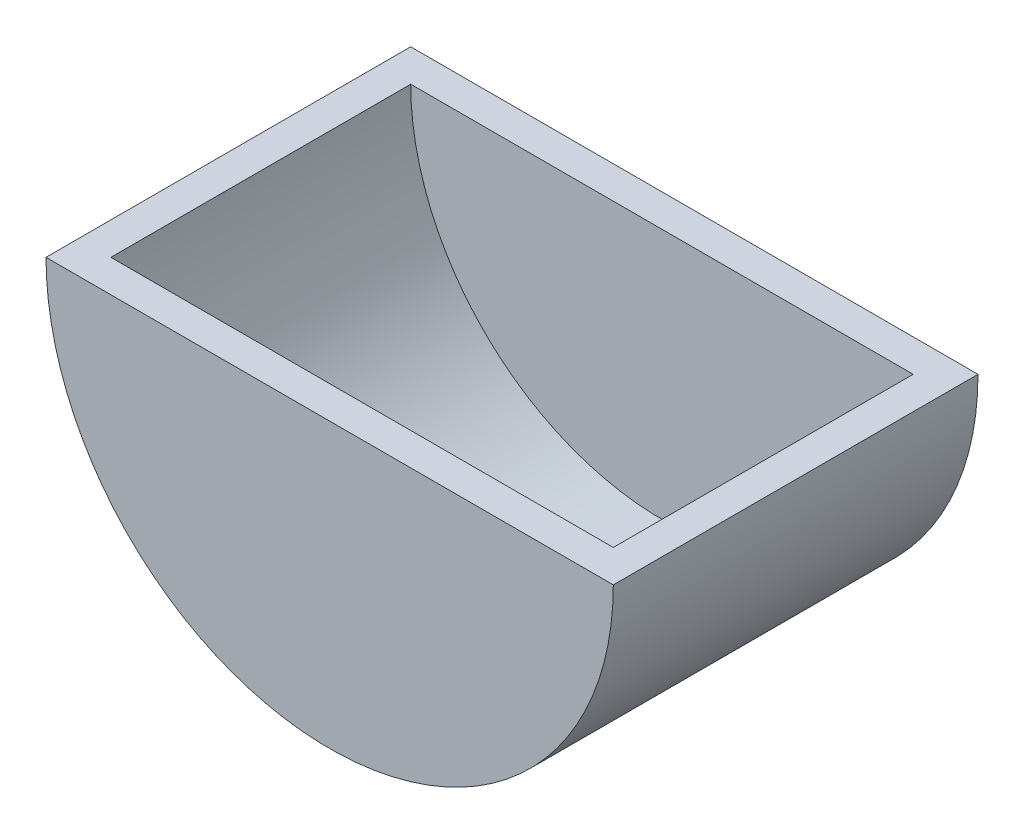
SolidWorks part; units mm, degrees
ref_plane "Front Plane" through (0, 0, 0) normal (0, 0, 1) x (1, 0, 0)
ref_plane "Top Plane" through (0, 0, 0) normal (0, 1, 0) x (1, 0, 0)
ref_plane "Right Plane" through (0, 0, 0) normal (1, 0, 0) x (0, 0, -1)
sketch "Sketch1" plane through (0, 0, 0) normal (0, 0, 1) x (1, 0, 0)
  line L0 (-35, 0) -> (35, 0)
  circle A0 centre (0, 0) radius 35
  dimension "D1" = 70
extrude "Boss-Extrude1" add sketch "Sketch1" along normal blind 45 contours L0 A0 region at (0, -14.8545, 0)
sketch "Sketch2" plane through (0, 0, 0) normal (0, 1, 0) x (1, 0, 0)
  line L0 (-35, 0) -> (35, 0) construction
  line L1 (-31, -4) -> (0.5147, -4)
  line L2 (-31, -4) -> (-31, -41)
  line L3 (-31, -41) -> (0, -41)
  line L5 (-35, -45) -> (35, -45) construction
  line L6 (-35, -45) -> (-35, 0) construction
  line L7 (0, 0) -> (0, -45) construction
  line L8 (-31, -4) -> (0.5147, -4)
  line L9 (-31, -4) -> (-31, -41)
  line L10 (-31, -41) -> (0, -41)
  line L13 (-31, -4) -> (0, -4)
  line L14 (-31, -4) -> (-31, -41)
  line L15 (-31, -41) -> (0, -41)
  line L16 (0, -4) -> (0, -41)
  dimension "D1" = 4
  dimension "D2" = 4
  dimension "D3" = 4
ref_axis "Axis1" through (0, 0, 45) along (0, 0, -1)
revolve "Cut-Revolve1" cut sketch "Sketch2" angle 360 about L7 region at (-15.5, 0, 22.5)
